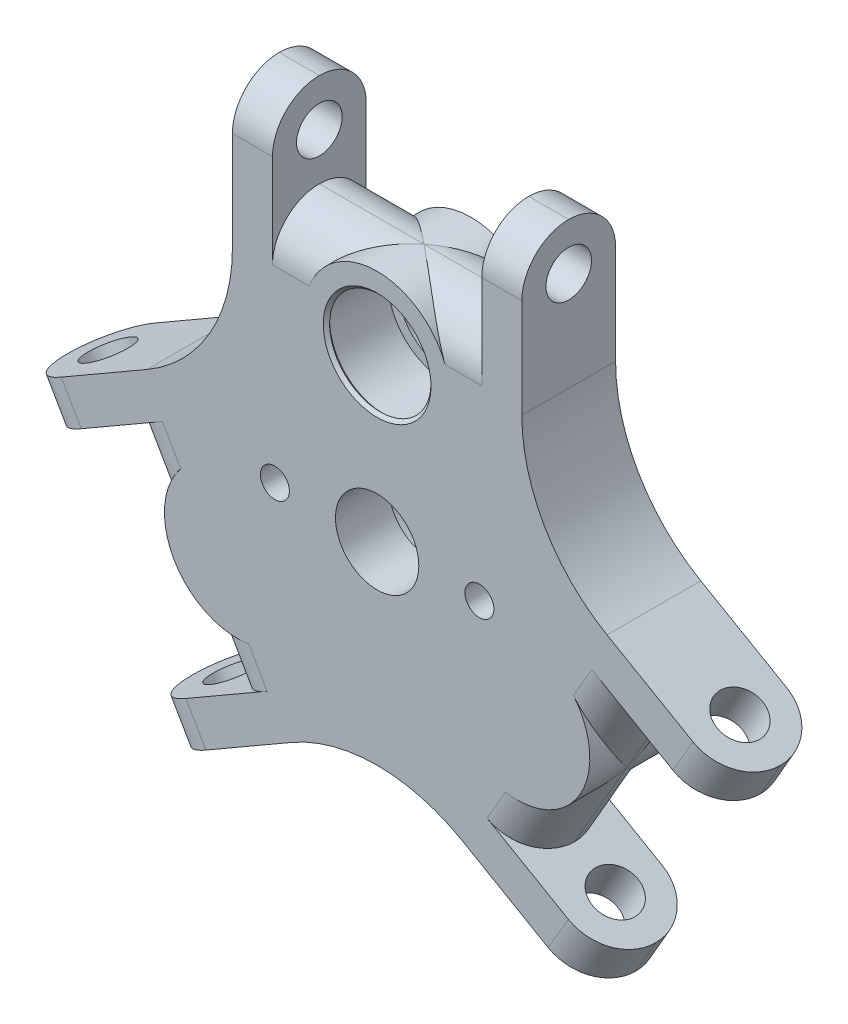
SolidWorks part; units mm, degrees
ref_plane "Front Plane" through (0, 0, 0) normal (0, 0, 1) x (1, 0, 0)
ref_plane "Top Plane" through (0, 0, 0) normal (0, 1, 0) x (1, 0, 0)
ref_plane "Right Plane" through (0, 0, 0) normal (1, 0, 0) x (0, 0, -1)
sketch "Sketch1" plane through (0, 0, 0) normal (0, 0, 1) x (1, 0, 0)
  line L0 (-16.9808, 38.5) -> (-12.2808, 38.5)
  line L1 (41.8324, -4.5442) -> (39.4824, -8.6145)
  line L2 (26.9808, 4.0303) -> (41.8324, -4.5442)
  line L3 (29.9561, -3.1145) -> (17.6753, -24.3855)
  line L4 (17.6753, -24.3855) -> (27.2016, -29.8855)
  line L5 (29.9561, -3.1145) -> (39.4824, -8.6145)
  line L6 (10, -25.3812) -> (24.8516, -33.9558)
  line L7 (0, -42) -> (0, 42) construction
  line L8 (-16.9808, 21.3509) -> (-16.9808, 38.5)
  line L9 (-12.2808, 27.5) -> (-12.2808, 38.5)
  line L10 (-24.8516, -33.9558) -> (-27.2016, -29.8855)
  line L11 (-10, -25.3812) -> (-24.8516, -33.9558)
  line L12 (-29.9561, -3.1145) -> (-39.4824, -8.6145)
  line L13 (-17.6753, -24.3855) -> (-27.2016, -29.8855)
  line L14 (24.8516, -33.9558) -> (27.2016, -29.8855)
  line L15 (-12.2808, 27.5) -> (12.2808, 27.5)
  line L16 (12.2808, 27.5) -> (12.2808, 38.5)
  line L17 (-29.9561, -3.1145) -> (-17.6753, -24.3855)
  line L18 (16.9808, 21.3509) -> (16.9808, 38.5)
  line L19 (-26.9808, 4.0303) -> (-41.8324, -4.5442)
  line L20 (16.9808, 38.5) -> (12.2808, 38.5)
  line L21 (-41.8324, -4.5442) -> (-39.4824, -8.6145)
  line L22 (14.6308, 38.5) -> (14.6308, 33) construction
  line L23 (14.6308, 33) -> (25.9808, 33) construction
  line L24 (25.9808, 33) -> (25.9808, 55.5294) construction
  line L25 (25.9808, 55.5294) -> (16.9808, 55.5294) construction
  circle A0 centre (0, 0) radius 42 construction
  arc A1 (-16.9808, 21.3509) -> (-26.9808, 4.0303) centre (-36.9808, 21.3509) cw
  arc A2 (16.9808, 21.3509) -> (26.9808, 4.0303) centre (36.9808, 21.3509) ccw
  arc A3 (-10, -25.3812) -> (10, -25.3812) centre (0, -42.7017) cw
  circle A5 centre (0, 0) radius 8.15
  point P17 (0, 27.5)
  dimension "D2" = 20
  dimension "D1" = 84
  dimension "D3" = 4.7
  dimension "D6" = 16.3
  dimension "D7" = 24.5615
  dimension "D4" = 120
  dimension "D5" = 120
extrude "Boss-Extrude1" add sketch "Sketch1" along normal blind 11 contours A5 region at (-14.6308, 37.3932, 0)
fillet "Fillet1" radius 5.5 6 edges at (-23.8157, -13.75, 0) (23.8157, -13.75, 0) (23.8157, -13.75, 11) (-23.8157, -13.75, 11) (0, 27.5, 0) (0, 27.5, 11)
sketch "Sketch5" plane through (0, 0, 0) normal (0, 0, -1) x (-1, 0, 0)
  circle A1 centre (0, 18.9655) radius 8.5345
extrude "Boss-Extrude2" add sketch "Sketch5" against normal blind 11
sketch "Sketch6" plane through (0, 0, 0) normal (0, 0, -1) x (-1, 0, 0)
  line L0 (-16.4246, -9.4827) -> (-19.0526, -11)
  circle A0 centre (0, 0) radius 18.9655
  circle A1 centre (-16.4246, -9.4827) radius 8.5345
extrude "Boss-Extrude3" add sketch "Sketch6" against normal blind 11 contours A0 A1 | A0 A1 L0 | A1 A0 L0 | A1 region at (13.0078, -7.5101, 0) region at (19.2429, -11.1099, 0)
sketch "Sketch7" plane through (0, 0, 11) normal (0, 0, 1) x (1, 0, 0)
  line L0 (-16.4246, -9.4827) -> (-19.0526, -11) construction
  circle A0 centre (0, 0) radius 18.9655 construction
  circle A1 centre (-16.4246, -9.4827) radius 8.5345
extrude "Boss-Extrude4" add sketch "Sketch7" against normal blind 11
sketch "Sketch8" plane through (0, 0, 11) normal (0, 0, 1) x (1, 0, 0)
  circle A0 centre (0, 0) radius 12 construction
  circle A1 centre (-12, 0) radius 1.7
  circle A2 centre (12, 0) radius 1.7
  dimension "D1" = 24
  dimension "D2" = 3.4
extrude "Cut-Extrude4" cut sketch "Sketch8" against normal through all
sketch "Sketch12" plane through (0, 0, 11) normal (0, 0, 1) x (1, 0, 0)
  circle A0 centre (0, 0) radius 8.15
  dimension "D1" = 16.3
extrude "Boss-Extrude5" add sketch "Sketch12" against normal blind 6.25
sketch "Sketch14" plane through (0, 0, 11) normal (0, 0, 1) x (1, 0, 0)
  circle A0 centre (0, 0) radius 4.8895
  dimension "D1" = 9.779
extrude "Cut-Extrude7" cut sketch "Sketch14" against normal through all
sketch "Sketch15" plane through (0, 0, 11) normal (0, 0, 1) x (1, 0, 0)
  circle A1 centre (0, 18.9655) radius 6.7
  dimension "D1" = 13.4
extrude "Cut-Extrude8" cut sketch "Sketch15" against normal blind 8
sketch "Sketch16" plane through (0, 0, 3) normal (0, 0, 1) x (1, 0, 0)
  circle A0 centre (0, 18.9655) radius 5.5
  dimension "D1" = 11
extrude "Cut-Extrude9" cut sketch "Sketch16" against normal through all
sketch "Sketch18" plane through (0, 0, 11) normal (0, 0, 1) x (1, 0, 0)
  circle A0 centre (0, 18.9655) radius 6.7
  circle A1 centre (0, 18.9655) radius 5.95
  dimension "D1" = 0.75
extrude "Boss-Extrude6" add sketch "Sketch18" against normal blind 0.75
chamfer "Chamfer1" distance 0.375 angle 45 1 edges at (5.95, 18.9655, 11)
chamfer "Chamfer2" distance 0.375 angle 45 1 edges at (5.95, 18.9655, 10.25)
fillet "Fillet2" radius 5.5 12 edges at (26.0266, -31.9206, 0) (40.6574, -6.5794, 0) (26.0266, -31.9206, 11) (40.6574, -6.5794, 11) (14.6308, 38.5, 11) (14.6308, 38.5, 0) (-40.6574, -6.5794, 11) (-26.0266, -31.9206, 11) (-26.0266, -31.9206, 0) (-40.6574, -6.5794, 0) (-14.6308, 38.5, 11) (-14.6308, 38.5, 0)
sketch "Sketch19" plane through (-16.9808, 0, 0) normal (-1, 0, 0) x (0, 0, 1)
  circle A0 centre (5.5, 33) radius 2.675
  dimension "D1" = 5.35
extrude "Cut-Extrude10" cut sketch "Sketch19" against normal through all
sketch "Sketch20" plane through (-8.4904, 14.7058, 0) normal (-0.5, 0.866, 0) x (0.866, 0.5, 0)
  circle A0 centre (-33, -5.5) radius 2.675
  dimension "D1" = 5.35
extrude "Cut-Extrude11" cut sketch "Sketch20" against normal through all
sketch "Sketch21" plane through (-8.4904, -14.7058, 0) normal (-0.5, -0.866, 0) x (0.866, -0.5, 0)
  circle A0 centre (33, 5.5) radius 2.675
  dimension "D1" = 5.35
extrude "Cut-Extrude12" cut sketch "Sketch21" against normal through all
